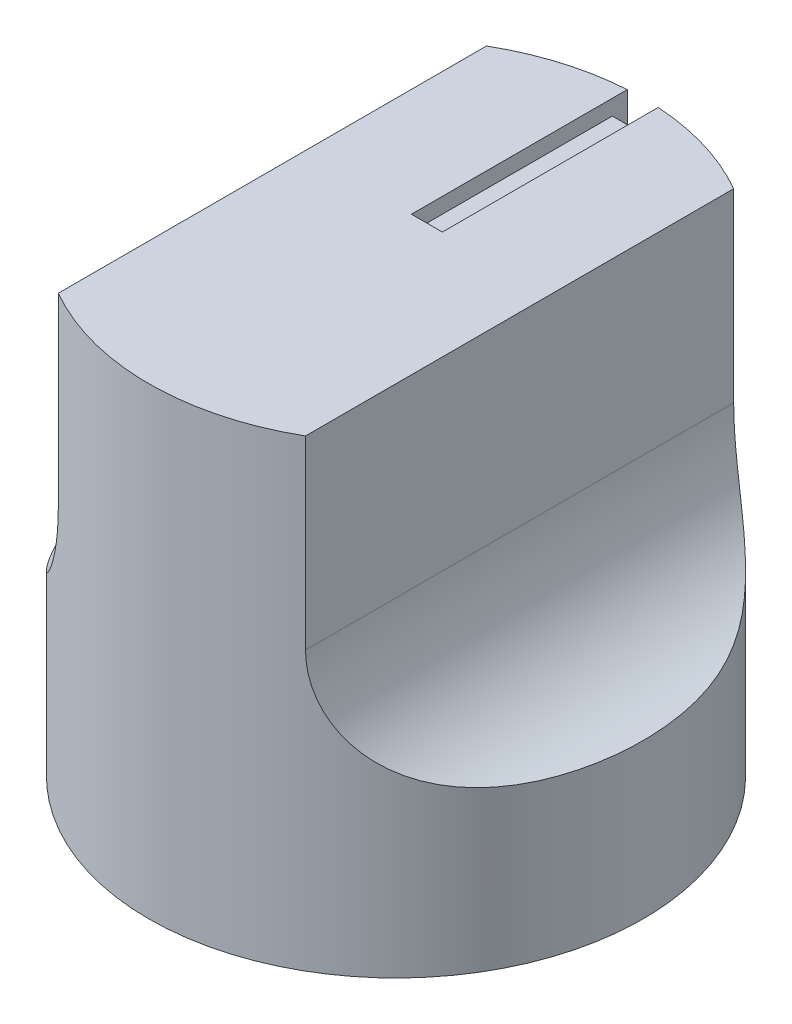
SolidWorks part; units mm, degrees
ref_plane "Front Plane" through (0, 0, 0) normal (0, 0, 1) x (1, 0, 0)
ref_plane "Top Plane" through (0, 0, 0) normal (0, 1, 0) x (1, 0, 0)
ref_plane "Right Plane" through (0, 0, 0) normal (1, 0, 0) x (0, 0, -1)
sketch "Sketch1" plane through (0, 0, 0) normal (0, 1, 0) x (1, 0, 0)
  circle A0 centre (0, 0) radius 8
  dimension "D1" = 16
extrude "Boss-Extrude1" add sketch "Sketch1" along normal blind 15
ref_plane "Plane1" through (0, 0, 10) normal (0, 0, 1) x (1, 0, 0)
sketch "Sketch2" plane through (0, 0, 10) normal (0, 0, 1) x (1, 0, 0)
  line L0 (8, 15) -> (-8, 15) construction
  line L2 (-4, 15) -> (-4, 9)
  line L4 (4, 15) -> (4, 9)
  line L5 (-8, 15) -> (-8, 0) construction
  line L9 (-8, 5) -> (-8, 15)
  line L10 (8, 0) -> (8, 15) construction
  line L13 (-8, 15) -> (-4, 15)
  line L14 (4, 15) -> (8, 15)
  line L15 (8, 15) -> (8, 5)
  arc A1 (-4, 9) -> (-8, 5) centre (-8, 9) cw
  arc A2 (4, 9) -> (8, 5) centre (8, 9) ccw
  dimension "D3" = 6
  dimension "D5" = 4
  dimension "D6" = 4
  dimension "D7" = 4
  dimension "D8" = 4
  dimension "D9" = 16
extrude "Cut-Extrude1" cut sketch "Sketch2" against normal blind 25
sketch "Sketch3" plane through (0, 0, 0) normal (0, -1, 0) x (1, 0, 0)
  circle A0 centre (0, 0) radius 6.5
  circle A1 centre (0, 0) radius 3
  circle A2 centre (0, 0) radius 3.75
  dimension "D1" = 13
  dimension "D2" = 6
  dimension "D3" = 7.5
extrude "Cut-Extrude3" cut sketch "Sketch3" against normal blind 13 contours A1 region at (0, 0, 0)
extrude "Cut-Extrude4" cut sketch "Sketch3<3>" against normal blind 3 contours A0 A2 region at (-6.3162, 0, 0)
sketch "Sketch3<3>" plane through (0, 0, 0) normal (0, -1, 0) x (1, 0, 0) same geometry as "Sketch3"
sketch "Sketch5" plane through (0, 0, 0) normal (0, -1, 0) x (1, 0, 0)
  circle A0 centre (0, 0) radius 6.45
  circle A1 centre (0, 0) radius 3.8
  dimension "D1" = 7.6
  dimension "D2" = 12.9
extrude "Boss-Extrude2" add sketch "Sketch5" against normal blind 3 separate body
sketch "Sketch6" plane through (0, 15, 0) normal (0, 1, 0) x (1, 0, 0)
  line L1 (-0.5, 1) -> (0.5, 1)
  line L2 (-0.5, 1) -> (-0.5, 8)
  line L3 (-0.5, 8) -> (0.5, 8)
  line L4 (0.5, 1) -> (0.5, 8)
  point P6 (0.2789, 0.045)
  dimension "D1" = 1
  dimension "D2" = 0.5
  dimension "D3" = 0.5
  dimension "D4" = 7
extrude "Cut-Extrude5" cut sketch "Sketch6" against normal blind 0.5
ref_plane "Plane2" through (0, 0, -8) normal (0, 0, 1) x (1, 0, 0)
sketch "Sketch7" plane through (0, 0, -8) normal (0, 0, 1) x (1, 0, 0)
  line L0 (-8, 0) -> (8, 0) construction
  line L1 (0.5, 14.5) -> (-0.5, 14.5)
  line L2 (0.5, 14.5) -> (0.5, 0)
  line L3 (0.5, 0) -> (-0.5, 0)
  line L4 (-0.5, 14.5) -> (-0.5, 0)
  dimension "D1" = 1
extrude "Cut-Extrude8" cut sketch "Sketch7" along normal blind 0.5
